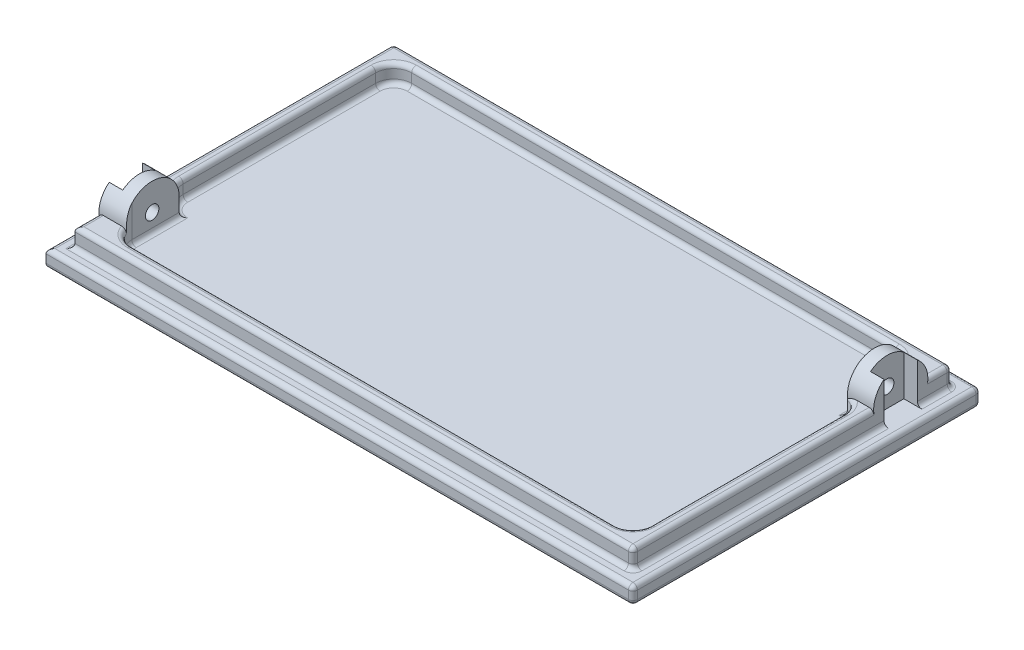
SolidWorks part; units mm, degrees
ref_plane "Alzado" through (0, 0, 0) normal (0, 0, 1) x (1, 0, 0)
ref_plane "Planta" through (0, 0, 0) normal (0, 1, 0) x (1, 0, 0)
ref_plane "Vista lateral" through (0, 0, 0) normal (1, 0, 0) x (0, 0, -1)
sketch "Croquis1" plane through (0, 0, 0) normal (0, 1, 0) x (1, 0, 0)
  line L1 (-65, -38.5) -> (65, -38.5)
  line L2 (-65, -38.5) -> (-65, 38.5)
  line L3 (-65, 38.5) -> (65, 38.5)
  line L4 (65, -38.5) -> (65, 38.5)
  line L5 (-65, -38.5) -> (65, 38.5) construction
  line L6 (-65, 38.5) -> (65, -38.5) construction
  point P0 (0, 0)
  dimension "D1" = 77
  dimension "D2" = 130
extrude "Saliente-Extruir1" add sketch "Croquis1" along normal blind 4 contours L2 L1 L4 L3
sketch "Croquis2" plane through (0, 4, 0) normal (0, 1, 0) x (1, 0, 0)
  line L0 (56, -29.5) -> (56, 29.5)
  line L1 (-62, -35.5) -> (62, -35.5)
  line L2 (-62, -35.5) -> (-62, 35.5)
  line L3 (-62, 35.5) -> (62, 35.5)
  line L4 (62, -35.5) -> (62, 35.5)
  line L5 (-62, -35.5) -> (62, 35.5) construction
  line L6 (-62, 35.5) -> (62, -35.5) construction
  line L7 (-56, 29.5) -> (56, 29.5)
  line L8 (-56, -29.5) -> (-56, 29.5)
  line L9 (-56, -29.5) -> (56, -29.5)
  line L10 (65, -38.5) -> (65, 38.5) construction
  line L11 (-65, 38.5) -> (65, 38.5) construction
  point P0 (0, 0)
  dimension "D2" = 3
  dimension "D3" = 3
  dimension "D1" = 6
extrude "Saliente-Extruir2" add sketch "Croquis2" along normal blind 4 contours L1 L4 L3 L2 L9 L8 L7 L0 region at (-60.5711, 4, 0)
sketch "Croquis3" plane through (62, 0, 0) normal (1, 0, 0) x (0, 0, -1)
  line L0 (-35.5, 8) -> (35.5, 8) construction
  line L1 (35.5, 8) -> (35.5, 4) construction
  circle A0 centre (24, 8) radius 6
  dimension "D1" = 12
  dimension "D2" = 11.5
extrude "Saliente-Extruir3" add sketch "Croquis3" against normal up to surface (6 mm away) up to face at (56, 6, 0)
sketch "Croquis4" plane through (-62, 0, 0) normal (-1, 0, 0) x (0, 0, 1)
  line L0 (35.5, 8) -> (-35.5, 8) construction
  line L1 (35.5, 8) -> (35.5, 4) construction
  circle A0 centre (24, 8) radius 6
  dimension "D1" = 12
  dimension "D2" = 11.5
extrude "Saliente-Extruir4" add sketch "Croquis4" against normal up to surface (6 mm away) up to face at (-56, 6, 0)
sketch "Croquis5" plane through (62, 0, 0) normal (1, 0, 0) x (0, 0, -1)
  circle A0 centre (24, 8) radius 1.5
  arc A1 (30, 8) -> (18, 8) centre (24, 8) ccw construction
  dimension "D1" = 3
extrude "Cortar-Extruir1" cut sketch "Croquis5" against normal up to surface (6 mm away) up to face at (56, 7.6667, -8)
sketch "Croquis7" plane through (-62, 0, 0) normal (-1, 0, 0) x (0, 0, 1)
  circle A0 centre (24, 8) radius 1.5
  arc A1 (30, 8) -> (18, 8) centre (24, 8) ccw construction
  dimension "D1" = 3
extrude "Cortar-Extruir2" cut sketch "Croquis7" against normal up to surface (6 mm away) up to face at (-56, 7.6667, 8)
sketch "Croquis10" plane through (0, 4, 0) normal (0, 1, 0) x (1, 0, 0)
  line L0 (-62, -35.5) -> (-62, 35.5) construction
  line L1 (-59, -27.5) -> (-62, -27.5)
  line L2 (-59, -27.5) -> (-59, -20.5)
  line L3 (-59, -20.5) -> (-62, -20.5)
  line L4 (-62, -27.5) -> (-62, -20.5)
  line L5 (-59, -27.5) -> (-62, -20.5) construction
  line L6 (-59, -20.5) -> (-62, -27.5) construction
  line L7 (-62, -18) -> (-62, -30) construction
  line L8 (62, 18) -> (62, 30) construction
  line L9 (59, 20.5) -> (62, 20.5)
  line L10 (59, 20.5) -> (59, 27.5)
  line L11 (59, 27.5) -> (62, 27.5)
  line L12 (62, 20.5) -> (62, 27.5)
  line L13 (59, 20.5) -> (62, 27.5) construction
  line L14 (59, 27.5) -> (62, 20.5) construction
  point P0 (-60.5, -24)
  point P9 (60.5, 24)
  point P16 (-62, -24)
  point P17 (62, 24)
  dimension "D1" = 3
  dimension "D2" = 3
  dimension "D3" = 7
  dimension "D4" = 7
extrude "Cortar-Extruir3" cut sketch "Croquis10" along normal blind 10
sketch "Croquis11" plane through (0, 4, 0) normal (0, 1, 0) x (1, 0, 0)
  line L0 (56, -29.5) -> (56, 29.5) construction
  line L1 (-56, -32.5) -> (56, -32.5)
  line L2 (-56, -32.5) -> (-56, 32.5)
  line L3 (-56, 32.5) -> (56, 32.5)
  line L4 (56, -32.5) -> (56, 32.5)
  line L5 (-56, -32.5) -> (56, 32.5) construction
  line L6 (-56, 32.5) -> (56, -32.5) construction
  line L7 (-62, 35.5) -> (62, 35.5) construction
  line L9 (-56, -32.5) -> (59, -32.5)
  line L10 (-56, -32.5) -> (-56, 18)
  line L11 (-56, 18) -> (59, 18)
  line L12 (59, -32.5) -> (59, 18)
  line L13 (56, 18) -> (62, 18) construction
  line L14 (-56, -18) -> (-62, -18) construction
  line L15 (-59, -18) -> (56, -18)
  line L16 (-59, -18) -> (-59, 32.5)
  line L17 (-59, 32.5) -> (56, 32.5)
  line L18 (56, -18) -> (56, 32.5)
  point P0 (0, 0)
  line M9 (-56, -29.5) -> (56, -29.5)
  line M11 (56, 29.5) -> (-56, 29.5)
  dimension "D1" = 3
extrude "Cortar-Extruir4" cut sketch "Croquis11" along normal blind 10 contours L4 L3 L2 M11 | L1 L4 L2 M9 | L10 L11 L12 L9 | L4 L3 L2 L1 | L16 L15 L18 L17 region at (0, 4, 31) region at (0, 4, -31)
sketch "Croquis9" plane through (0, 4, 0) normal (0, 1, 0) x (1, 0, 0)
  line L8 (61.8, -35.3) -> (61.8, 20.3)
  line L9 (61.8, 20.3) -> (58.8, 20.3)
  line L10 (58.8, 20.3) -> (58.8, 27.7)
  line L11 (58.8, 27.7) -> (61.8, 27.7)
  line L20 (61.8, 27.7) -> (61.8, 35.3)
  line L21 (61.8, 35.3) -> (-61.8, 35.3)
  line L22 (-61.8, 35.3) -> (-61.8, -20.3)
  line L23 (-61.8, -20.3) -> (-58.8, -20.3)
  line L24 (-58.8, -20.3) -> (-58.8, -27.7)
  line L25 (-58.8, -27.7) -> (-61.8, -27.7)
  line L26 (-61.8, -27.7) -> (-61.8, -35.3)
  line L27 (-61.8, -35.3) -> (61.8, -35.3)
  line L28 (62, -35.5) -> (62, 20.5)
  line L29 (-62, -35.5) -> (62, -35.5)
  line L30 (-62, -27.5) -> (-62, -35.5)
  line L31 (-59, -27.5) -> (-62, -27.5)
  line L32 (-59, -20.5) -> (-59, -27.5)
  line L33 (-62, -20.5) -> (-59, -20.5)
  line L34 (-62, 35.5) -> (-62, -20.5)
  line L35 (62, 35.5) -> (-62, 35.5)
  line L36 (62, 27.5) -> (62, 35.5)
  line L37 (59, 27.5) -> (62, 27.5)
  line L38 (59, 20.5) -> (59, 27.5)
  line L39 (62, 20.5) -> (59, 20.5)
  line L40 (62, -35.5) -> (62, 20.5)
  line L41 (-62, -35.5) -> (62, -35.5)
  line L42 (-62, -27.5) -> (-62, -35.5)
  line L43 (-59, -27.5) -> (-62, -27.5)
  line L44 (-59, -20.5) -> (-59, -27.5)
  line L45 (-62, -20.5) -> (-59, -20.5)
  line L46 (-62, 35.5) -> (-62, -20.5)
  line L47 (62, 35.5) -> (-62, 35.5)
  line L48 (62, 27.5) -> (62, 35.5)
  line L49 (59, 27.5) -> (62, 27.5)
  line L50 (59, 20.5) -> (59, 27.5)
  line L51 (62, 20.5) -> (59, 20.5)
  line M13 (62, 35.5) -> (62, 27.5)
  line M14 (62, -35.5) -> (-62, -35.5)
  line M15 (-62, -35.5) -> (-62, -27.5)
  line M16 (-62, 35.5) -> (62, 35.5)
  line M17 (62, 20.5) -> (62, -35.5)
  line M18 (-62, -27.5) -> (-59, -27.5)
  line M19 (-59, -27.5) -> (-59, -20.5)
  line M20 (-59, -20.5) -> (-62, -20.5)
  line M21 (-62, -20.5) -> (-62, 35.5)
  line M22 (62, 27.5) -> (59, 27.5)
  line M23 (59, 27.5) -> (59, 20.5)
  line M24 (59, 20.5) -> (62, 20.5)
  dimension "D1" = 0.2
  dimension "D2" = 0
extrude "PrintMatch" cut sketch "Croquis9" along normal through all contours L27 L26 L25 L24 L23 L22 L21 L20 L11 L10 L9 L8 M17 M24 M23 M22 M13 M16 M21 M20 M19 M18 M15 M14
sketch "Croquis12" plane through (0, 4, 0) normal (0, 1, 0) x (1, 0, 0)
  line L0 (-71.8, 45.3) -> (-71.8, -24)
  line L1 (-71.8, -24) -> (-71.8, -24)
  line L2 (-71.8, -24) -> (-71.8, -24)
  line L3 (-71.8, -24) -> (-71.8, -24)
  line L4 (-71.8, -24) -> (-71.8, -45.3)
  line L5 (-71.8, -45.3) -> (71.8, -45.3)
  line L6 (71.8, -45.3) -> (71.8, 24)
  line L7 (71.8, 24) -> (71.8, 24)
  line L8 (71.8, 24) -> (71.8, 24)
  line L9 (71.8, 24) -> (71.8, 24)
  line L10 (71.8, 24) -> (71.8, 45.3)
  line L11 (71.8, 45.3) -> (-71.8, 45.3)
  line L12 (-61.8, -35.3) -> (61.8, -35.3)
  line L13 (-61.8, -27.7) -> (-61.8, -35.3)
  line L14 (-58.8, -27.7) -> (-61.8, -27.7)
  line L15 (-58.8, -20.3) -> (-58.8, -27.7)
  line L16 (-61.8, -20.3) -> (-58.8, -20.3)
  line L17 (-61.8, 35.3) -> (-61.8, -20.3)
  line L18 (61.8, 35.3) -> (-61.8, 35.3)
  line L19 (61.8, 27.7) -> (61.8, 35.3)
  line L20 (58.8, 27.7) -> (61.8, 27.7)
  line L21 (58.8, 20.3) -> (58.8, 27.7)
  line L22 (61.8, 20.3) -> (58.8, 20.3)
  line L23 (61.8, -35.3) -> (61.8, 20.3)
  line L24 (-61.8, -35.3) -> (61.8, -35.3)
  line L25 (-61.8, -27.7) -> (-61.8, -35.3)
  line L26 (-58.8, -27.7) -> (-61.8, -27.7)
  line L27 (-58.8, -20.3) -> (-58.8, -27.7)
  line L28 (-61.8, -20.3) -> (-58.8, -20.3)
  line L29 (-61.8, 35.3) -> (-61.8, -20.3)
  line L30 (61.8, 35.3) -> (-61.8, 35.3)
  line L31 (61.8, 27.7) -> (61.8, 35.3)
  line L32 (58.8, 27.7) -> (61.8, 27.7)
  line L33 (58.8, 20.3) -> (58.8, 27.7)
  line L34 (61.8, 20.3) -> (58.8, 20.3)
  line L35 (61.8, -35.3) -> (61.8, 20.3)
  dimension "D1" = 0
  dimension "D2" = 10
extrude "Cortar-Extruir5" cut sketch "Croquis12" against normal blind 0.2
fillet "Redondeo1" [suppressed] radius 8
fillet "Redondeo2" radius 4 6 edges at (56, 6, -32.5) (59, 6, -18) (59, 6, 32.5) (-56, 6, 32.5) (-59, 6, -32.5) (-59, 6, 18)
fillet "Redondeo6" radius 1 48 edges at (65, 1.9, -38.5) (0, 0, -38.5) (0, 0, 38.5) (65, 0, 0) (-65, 1.9, -38.5) (-65, 0, 0) (56, 4, -23.25) (-56, 4, 23.25) (0, 8, -35.3) (0, 3.8, 38.5) (65, 3.8, 0) (-59, 4, -7.1865) (-1.5, 4, -32.5) (59, 4, 7.1865) (1.5, 4, 32.5) (-65, 3.8, 0) (0, 3.8, -38.5) (61.8, 8, -32.65) (61.8, 3.8, 7.5) (61.8, 3.8, -31.5) (-58.1623, 8, 16.5765) (-59, 8, -7.1865) (54.2361, 8, -31.8166) (58.1623, 8, -16.5765) (59, 8, 7.1865) (-54.2361, 8, 31.8166) (-1.5, 8, -32.5) (-57.8284, 8, -31.3284) (1.5, 8, 32.5) (57.8284, 8, 31.3284) (0, 8, 35.3) (0, 3.8, 35.3) (61.8, 8, 8.65) (61.8, 5.9, 35.3) (65, 1.9, 38.5) (61.8, 5.9, -35.3) (0, 3.8, -35.3) (-61.8, 5.9, -35.3) (-61.8, 8, -8.65) (-61.8, 3.8, -7.5) (-61.8, 3.8, 31.5) (-61.8, 8, 32.65) (-57.8284, 4, -31.3284) (54.8284, 4, -31.3284) (58.1623, 4, -16.5765) (57.8284, 4, 31.3284) (-54.8284, 4, 31.3284) (-58.1623, 4, 16.5765)
